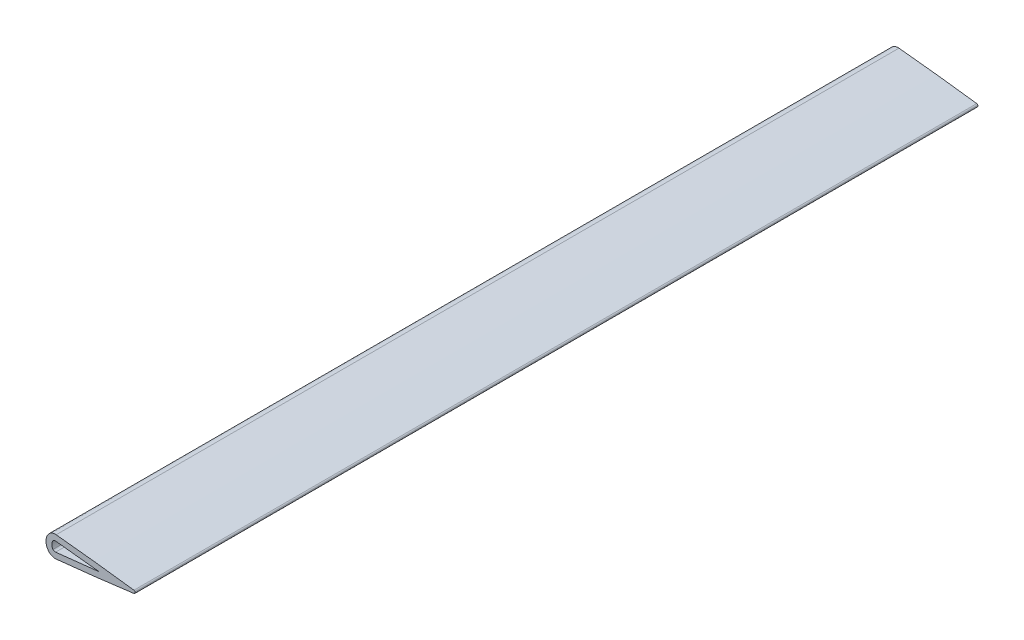
SolidWorks part; units mm, degrees
material "ABS"
ref_plane "Front Plane" through (0, 0, 0) normal (0, 0, 1) x (1, 0, 0)
ref_plane "Top Plane" through (0, 0, 0) normal (0, 1, 0) x (1, 0, 0)
ref_plane "Right Plane" through (0, 0, 0) normal (1, 0, 0) x (0, 0, -1)
sketch "Sketch2" plane through (0, 0, 125) normal (0, 0, 1) x (1, 0, 0)
  line L6 (72.8985, 242.6983) -> (74.0667, 242.8596)
  line L7 (74.0667, 242.8596) -> (72.8985, 243.0209)
  arc A0 (42.4402, 246.6168) -> (42.4403, 239.1025) centre (44.0667, 242.8596) ccw
  spline S4 degree 3 poles (72.8985, 243.0209) (68.2268, 243.666) (58.8702, 244.8607) (48.7077, 245.9849) (43.2279, 246.5384) (42.4402, 246.6168) knots 0.003074 0.003074 0.003074 0.003074 0.064763 0.126452 0.136805 0.136805 0.136805 0.136805
  spline S5 degree 3 poles (42.4403, 239.1025) (43.2279, 239.1809) (48.7077, 239.7343) (58.8701, 240.8588) (68.2267, 242.0534) (72.8985, 242.6983) knots 0.856366 0.856366 0.856366 0.856366 0.866719 0.928408 0.990097 0.990097 0.990097 0.990097
extrude "Boss-Extrude1" add sketch "Sketch2" along normal mid plane 292
fillet "Fillet1" radius 3 2 edges at (42.4403, 239.1025, 125) (42.4402, 246.6168, 125)
sketch "Sketch5" plane through (0, 0, 271) normal (0, 0, 1) x (1, 0, 0)
  arc A6 (42.4055, 244.1346) -> (42.4055, 241.5847) centre (44.0667, 242.8596) ccw
  arc A7 (42.4055, 241.5847) -> (43.2991, 241.1985) centre (43.1988, 242.1935) ccw
  arc A8 (43.2991, 244.5207) -> (42.4055, 244.1346) centre (43.1988, 243.5257) ccw
  arc A9 (42.4055, 244.1346) -> (42.4055, 241.5847) centre (44.0667, 242.8596) ccw
  arc A10 (42.4055, 241.5847) -> (43.2991, 241.1985) centre (43.1988, 242.1935) ccw
  arc A11 (43.2991, 244.5207) -> (42.4055, 244.1346) centre (43.1988, 243.5257) ccw
  spline S4 degree 3 poles (2861.3701, -2544.8866) (-5145.0627, 4423.3205) (2629.1087, -3992.6803) (320.6233, 3941.4993) knots -200.875743 -200.875743 -200.875743 -200.875743 118.902758 118.902758 118.902758 118.902758 only from (43.2991, 241.1985) to (58.4244, 242.8597)
  spline S5 degree 3 poles (1185.4758, -3407.8825) (1000.8046, 4063.6158) (-1881.0107, -3339.9525) (-1651.9487, 2926.2625) knots -110.814992 -110.814992 -110.814992 -110.814992 169.109579 169.109579 169.109579 169.109579 only from (58.4244, 242.8597) to (43.2991, 244.5207)
  spline S6 degree 3 poles (43.2991, 241.1985) (48.3457, 241.7074) (53.3878, 242.2608) (58.4244, 242.8597) knots 0 0 0 0 1 1 1 1
  spline S7 degree 3 poles (58.4244, 242.8597) (53.3877, 243.4586) (48.3458, 244.0118) (43.2991, 244.5207) knots 0 0 0 0 1 1 1 1
  dimension "D1" = 2
extrude "Cut-Extrude2" cut sketch "Sketch5" against normal up to surface (292 mm away) up to face at (55.3363, 242.3611, -21)
sketch "Sketch3" plane through (0, 242.8596, 0) normal (0, -1, 0) x (1, 0, 0)
  line L0 (74.0667, 125) -> (21.6985, 125) construction
  line L1 (24.3034, 205) -> (59.3034, 205)
  line L2 (24.3034, 205) -> (24.3034, 185)
  line L3 (24.3034, 185) -> (59.3034, 185)
  line L4 (59.3034, 205) -> (59.3034, 185)
  line L5 (74.0667, 271) -> (74.0667, -21) construction
  line L6 (59.3034, 45) -> (59.3034, 65)
  line L7 (24.3034, 65) -> (59.3034, 65)
  line L8 (24.3034, 45) -> (24.3034, 65)
  line L9 (24.3034, 45) -> (59.3034, 45)
extrude "Cut-Extrude1" cut sketch "Sketch3" along normal through all
fillet "Fillet2" radius 3 4 edges at (59.3034, 241.905, 185) (59.3034, 241.905, 205) (59.3034, 241.905, 65) (59.3034, 241.905, 45)
fillet "Fillet3" radius 0.5 1 edges at (74.0667, 242.8596, 125)
